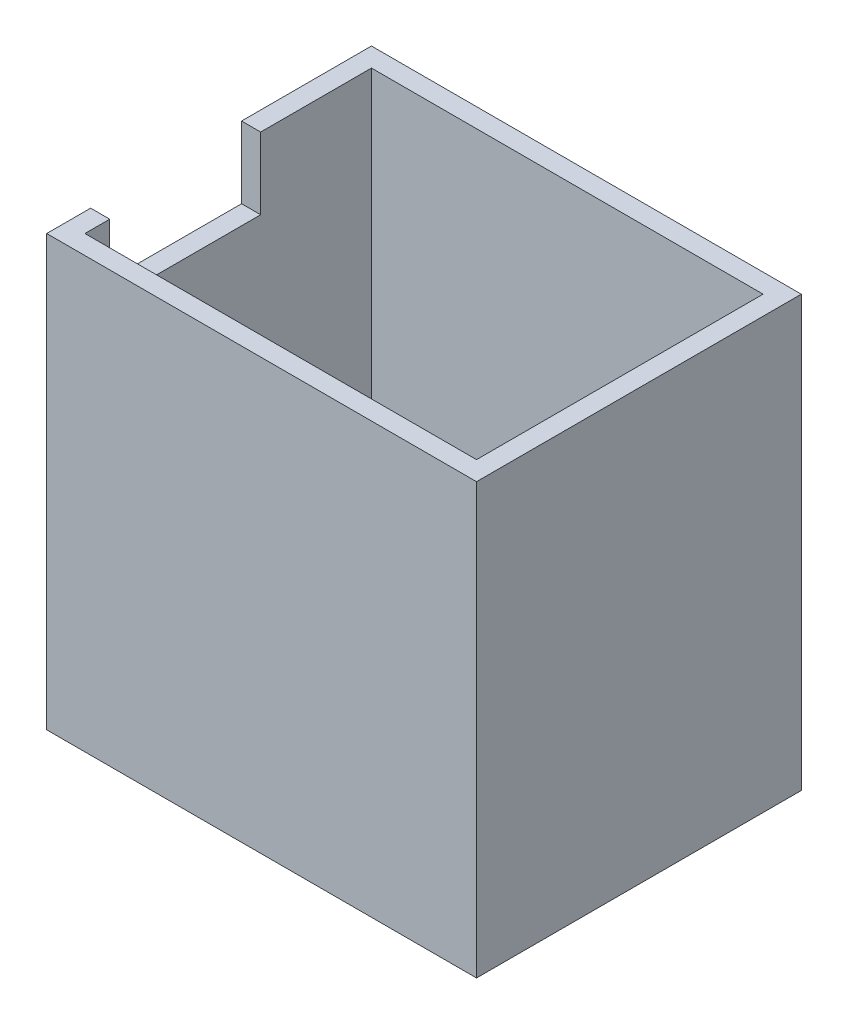
SolidWorks part; units mm, degrees
ref_plane "Front Plane" through (0, 0, 0) normal (0, 0, 1) x (1, 0, 0)
ref_plane "Top Plane" through (0, 0, 0) normal (0, 1, 0) x (1, 0, 0)
ref_plane "Right Plane" through (0, 0, 0) normal (1, 0, 0) x (0, 0, -1)
sketch "Sketch1" plane through (0, 0, 0) normal (0, 1, 0) x (1, 0, 0)
  line L1 (-28.575, -21.59) -> (28.575, -21.59)
  line L2 (-28.575, -21.59) -> (-28.575, 21.59)
  line L3 (-28.575, 21.59) -> (28.575, 21.59)
  line L4 (28.575, -21.59) -> (28.575, 21.59)
  line L5 (-28.575, -21.59) -> (28.575, 21.59) construction
  line L6 (-28.575, 21.59) -> (28.575, -21.59) construction
  point P0 (0, 0)
  dimension "D1" = 57.15
  dimension "D2" = 43.18
extrude "Base" add sketch "Sketch1" along normal blind 57.15
sketch "Sketch2" plane through (0, 57.15, 0) normal (0, 1, 0) x (1, 0, 0)
  line L1 (26.035, -19.05) -> (-26.035, -19.05)
  line L2 (26.035, -19.05) -> (26.035, 19.05)
  line L3 (26.035, 19.05) -> (-26.035, 19.05)
  line L4 (-26.035, -19.05) -> (-26.035, 19.05)
  line L5 (26.035, -19.05) -> (-26.035, 19.05) construction
  line L6 (26.035, 19.05) -> (-26.035, -19.05) construction
  point P0 (0, 0)
  dimension "D1" = 38.1
  dimension "D2" = 52.07
extrude "Pocket" cut sketch "Sketch2" against normal blind 47.9552
sketch "Sketch3" plane through (0, 0, 0) normal (0, -1, 0) x (-1, 0, 0)
  line L0 (28.575, 0) -> (-28.575, 0) construction
  line L1 (7.493, -7.747) -> (-10.795, -7.747)
  line L2 (7.493, -7.747) -> (7.493, 7.747)
  line L3 (7.493, 7.747) -> (-10.795, 7.747)
  line L4 (-10.795, -7.747) -> (-10.795, 7.747)
  line L5 (7.493, -7.747) -> (-10.795, 7.747) construction
  line L6 (7.493, 7.747) -> (-10.795, -7.747) construction
  line L7 (28.575, 21.59) -> (28.575, -21.59) construction
  line L8 (-28.575, -21.59) -> (-28.575, 21.59) construction
  point P0 (-1.651, 0)
  dimension "D1" = 15.494
  dimension "D2" = 18.288
  dimension "D3" = 21.082
extrude "LinActHole" cut sketch "Sketch3" against normal through all
sketch "Sketch4" plane through (-28.575, 0, 0) normal (-1, 0, 0) x (0, 0, 1)
  line L0 (-21.59, 57.15) -> (21.59, 57.15) construction
  line L1 (15.748, 57.15) -> (-4.318, 57.15)
  line L2 (15.748, 57.15) -> (15.748, 47.625)
  line L3 (15.748, 47.625) -> (-4.318, 47.625)
  line L4 (-4.318, 57.15) -> (-4.318, 47.625)
  line L5 (21.59, 57.15) -> (21.59, 0) construction
  line L6 (-21.59, 57.15) -> (-21.59, 0) construction
  dimension "D1" = 5.842
  dimension "D2" = 17.272
  dimension "D3" = 9.525
extrude "RollMotorHole" cut sketch "Sketch4" against normal up to next
sketch "Sketch5" plane through (0, 0, 0) normal (0, -1, 0) x (1, 0, 0)
  line L1 (17.6249, -13.716) -> (24.2289, -13.716)
  line L2 (15.0849, -11.176) -> (15.0849, 11.176)
  line L3 (17.6249, 13.716) -> (24.2289, 13.716)
  line L4 (24.2289, -13.716) -> (24.2289, 13.716)
  line L5 (15.0849, -13.716) -> (24.2289, 13.716) construction
  line L6 (15.0849, 13.716) -> (24.2289, -13.716) construction
  arc A0 (15.0849, -11.176) -> (17.6249, -13.716) centre (17.6249, -11.176) ccw
  arc A1 (15.0849, 11.176) -> (17.6249, 13.716) centre (17.6249, 11.176) cw
  point P0 (19.6569, 0)
  dimension "D3" = 2.54
  dimension "D1" = 27.432
  dimension "D2" = 9.144
extrude "DviHole" cut sketch "Sketch5" against normal up to next
hole_wizard "CBORE for #4 Socket Head Cap Screw1" positions "Sketch7" profile "Sketch6" counterbore size "#4" standard "ANSI Inch" end condition through all
sketch "Sketch7" plane through (0, 0, 0) normal (0, -1, 0) x (-1, 0, 0)
  line L0 (-19.6569, 21.59) -> (-19.6569, -21.59) construction
  line L1 (-28.575, 21.59) -> (28.575, 21.59) construction
  line L2 (28.575, -21.59) -> (-28.575, -21.59) construction
  line L3 (-24.2289, 13.716) -> (-24.2289, -13.716) construction
  line L4 (-24.2289, 0) -> (-15.0849, 0) construction
  line L5 (-15.0849, -11.176) -> (-15.0849, 11.176) construction
  point P0 (-19.6569, 16.256)
  point P2 (-19.6569, -16.256)
  dimension "D1" = 4.572
  dimension "D2" = 32.512
sketch "Sketch6" plane through (19.6569, 0, -16.256) normal (1, 0, 0) x (0, 0, -1)
  line L0 (0, 0) -> (0, 57.15)
  line L1 (0, 57.15) -> (1.6319, 57.15)
  line L3 (1.6319, 57.15) -> (1.632, 2.8448)
  line L4 (1.632, 2.8448) -> (2.7788, 2.8448)
  line L5 (2.7788, 2.8448) -> (2.7788, 0)
  line L7 (2.7788, 0) -> (0, 0)
  line L11 (0, -6.35) -> (0, 107.95) construction
  dimension "Thru Hole Dia." = 3.2639
  dimension "Thru Hole Depth" = 57.15
  dimension "C'Bore Dia." = 5.5575
  dimension "C'Bore Depth" = 2.8448
hole_wizard "CBORE for #8 Socket Head Cap Screw1" positions "Sketch9" profile "Sketch8" counterbore size "#8" standard "ANSI Inch" end condition through all
sketch "Sketch9" plane through (0, 0, 0) normal (0, -1, 0) x (-1, 0, 0)
  line L0 (3.175, -21.59) -> (3.175, 21.59) construction
  line L1 (28.575, -21.59) -> (-28.575, -21.59) construction
  line L2 (-28.575, 21.59) -> (28.575, 21.59) construction
  line L3 (28.575, 0) -> (-28.575, 0) construction
  line L4 (28.575, 21.59) -> (28.575, -21.59) construction
  line L5 (-28.575, -21.59) -> (-28.575, 21.59) construction
  point P0 (3.175, 14.605)
  point P2 (3.175, -14.605)
  dimension "D1" = 31.75
  dimension "D2" = 29.21
sketch "Sketch8" plane through (-3.175, 0, -14.605) normal (1, 0, 0) x (0, 0, -1)
  line L0 (0, 0) -> (0, 57.15)
  line L1 (0, 57.15) -> (2.2479, 57.15)
  line L3 (2.2479, 57.15) -> (2.2479, 4.1656)
  line L4 (2.2479, 4.1656) -> (3.9688, 4.1656)
  line L5 (3.9688, 4.1656) -> (3.9688, 0)
  line L7 (3.9688, 0) -> (0, 0)
  line L11 (0, -6.35) -> (0, 107.95) construction
  dimension "Thru Hole Dia." = 4.4958
  dimension "Thru Hole Depth" = 57.15
  dimension "C'Bore Dia." = 7.9375
  dimension "C'Bore Depth" = 4.1656
fillet "Fillet1" radius 0.254 4 edges at (20.7838, 1.4224, -13.716) (18.53, 1.4224, -13.716) (20.7838, 1.4224, 13.716) (18.53, 1.4224, 13.716)
